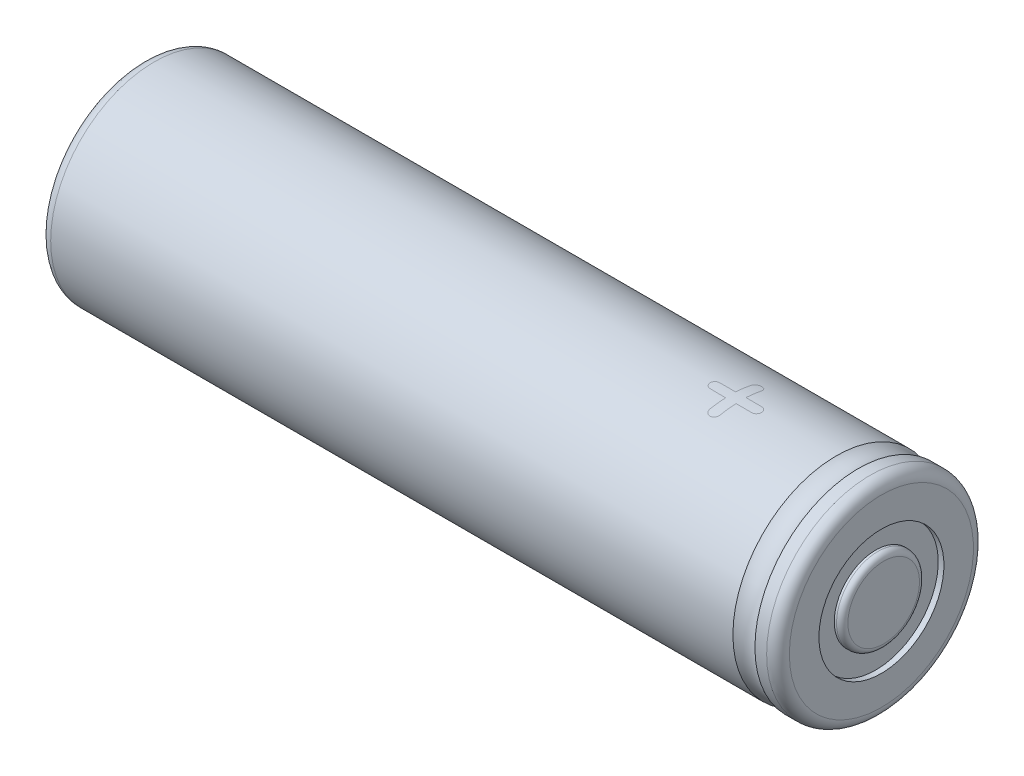
SolidWorks part; units mm, degrees
material "ABS_eSun_GRN"
ref_plane "Front Plane" through (0, 0, 0) normal (0, 0, 1) x (1, 0, 0)
ref_plane "Top Plane" through (0, 0, 0) normal (0, 1, 0) x (1, 0, 0)
ref_plane "Right Plane" through (0, 0, 0) normal (1, 0, 0) x (0, 0, -1)
sketch "Sketch1" plane through (0, 0, 0) normal (0, 1, 0) x (1, 0, 0)
  line L0 (0, 0) -> (115.0104, 0) construction
  line L1 (50, 0) -> (-50, 0) construction
  line L2 (-31.0159, -23.4) -> (-31.0159, 8.1) construction
  line L3 (-30.0159, 9.1) -> (30.0159, 9.1)
  line L4 (33.9841, 8.1) -> (33.9841, 0) construction
  line L5 (33.4846, 0) -> (-30.7159, 0)
  line L6 (31.9524, 9.1) -> (32.9841, 9.1)
  line L7 (-31.0159, 5.5) -> (-30.7159, 5.5)
  line L8 (-30.7159, 5.5) -> (-30.7159, 0)
  line L9 (-31.0159, 8.1) -> (-31.0159, 5.5)
  line L10 (30.0159, 9.1) -> (31.9524, 9.1) construction
  line L11 (33.9841, 5.5) -> (33.4846, 5.5)
  line L12 (33.4846, 5.5) -> (33.4846, 0)
  line L13 (33.9841, 8.1) -> (33.9841, 5.5)
  arc A0 (30.0159, 9.1) -> (31.9524, 9.1) centre (30.9841, 10.85) ccw
  arc A1 (32.9841, 9.1) -> (33.9841, 8.1) centre (32.9841, 8.1) cw
  arc A2 (-31.0159, 8.1) -> (-30.0159, 9.1) centre (-30.0159, 8.1) cw
  point P14 (33.9841, 9.1)
  point P17 (-31.0159, 9.1)
  point P20 (0, 9.1)
  point P22 (30.9841, 8.85)
  point P23 (30.9841, 9.1)
  dimension "D4" = 2
  dimension "D5" = 1
  dimension "D1" = 65
  dimension "D2" = 18.2
  dimension "D3" = 3
  dimension "D6" = 0.3
  dimension "D8" = 0.25
  dimension "D7" = 11
  dimension "D9" = 11
revolve "mainBody" add sketch "Sketch1" angle 360 about L0
sketch "Sketch2" plane through (0, 0, 0) normal (0, 1, 0) x (1, 0, 0)
  line L0 (33.4846, -5.5) -> (33.4846, 5.5) construction
  line L1 (33.4846, 0) -> (34.1841, 0)
  line L2 (33.4846, 0) -> (33.4846, 3.65)
  line L3 (33.4846, 3.65) -> (34.1841, 3.65)
  line L4 (34.1841, 0) -> (34.1841, 3.65)
  line L5 (33.4846, 0) -> (36.5558, 0) construction
  line L6 (33.9841, -8.1) -> (33.9841, 8.1) construction
  dimension "D1" = 7.3
  dimension "D2" = 0.2
revolve "Revolve2" add sketch "Sketch2" angle 360 about L5
fillet "Fillet1" radius 0.5 1 edges at (34.1841, 0, 3.65)
sketch "Sketch3" plane through (0, 0, 0) normal (0, 1, 0) x (1, 0, 0)
  line L0 (18, -3.15) -> (0, -3.15) construction
  line L1 (0, -3.15) -> (0, 0) construction
  text T0 "+" font "DS ISO 1" height 9
  dimension "D1" = 3.15
  dimension "D2" = 18
split line "Split Line1"
ref_axis "BATTERY" through (37.4441, 0, 0) along (-1, 0, 0)
equation "\"length\"= 65"
equation "\"D1@Sketch1\"=\"length\""
equation "\"diam\"= 18.2"
equation "\"D2@Sketch1\"=\"diam\""
equation "\"radius_corner\"=2"
equation "\"D4@Sketch1\"=\"radius_corner\""
equation "\"D9@Sketch1\"=\"D7@Sketch1\""
